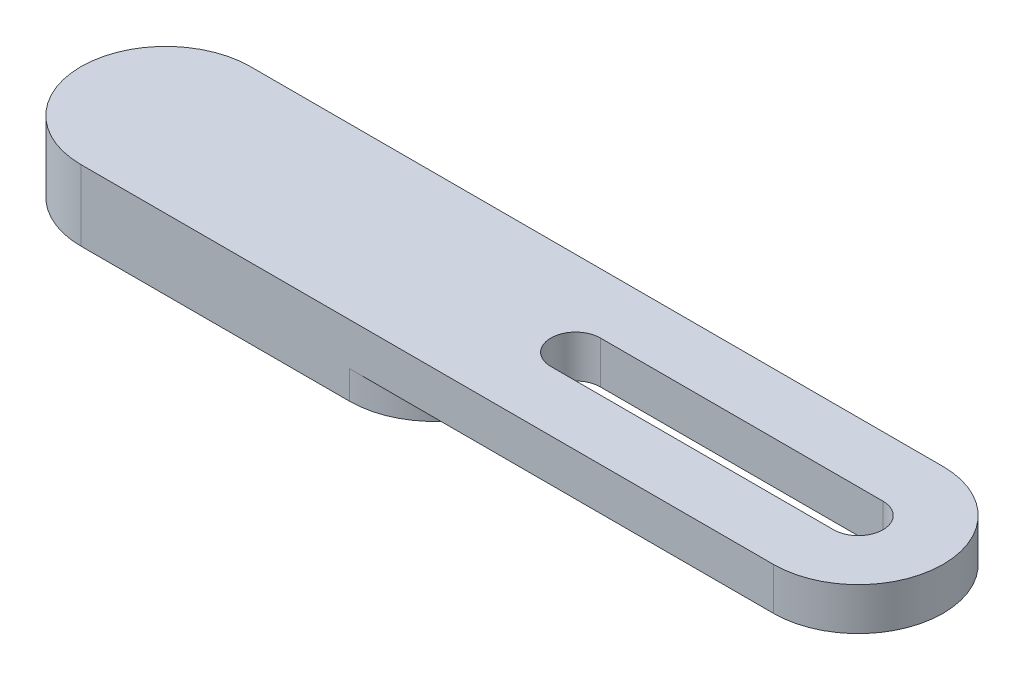
SolidWorks part; units mm, degrees
ref_plane "前视基准面" through (0, 0, 0) normal (0, 0, 1) x (1, 0, 0)
ref_plane "上视基准面" through (0, 0, 0) normal (0, 1, 0) x (1, 0, 0)
ref_plane "右视基准面" through (0, 0, 0) normal (1, 0, 0) x (0, 0, -1)
sketch "草图1" plane through (0, 0, 0) normal (0, 1, 0) x (1, 0, 0)
  line L0 (0, 0) -> (19, 0) construction
  line L1 (0.3158, 3.9875) -> (19.1974, 2.4922)
  line L2 (19.1974, -2.4922) -> (0.3158, -3.9875)
  line L3 (0, 0) -> (-4, 0) construction
  line L4 (19, 0) -> (21.5, 0) construction
  line L5 (19, 6) -> (0, 6)
  line L6 (0, -6) -> (19, -6)
  circle A0 centre (0, 0) radius 4
  circle A1 centre (19, 0) radius 2.5
  circle A2 centre (0, 0) radius 6
  circle A3 centre (19, 0) radius 6
  dimension "D1" = 8
  dimension "D2" = 5
  dimension "D3" = 25.5
  dimension "D4" = 12
  dimension "D5" = 12
extrude "凸台-拉伸1" add sketch "草图1" against normal blind 3 contours L5 | A2 L2 A0 L1 | A3 L5 A2 L1 | A3 L1 A1 L2 | A3 L2 A2 L6 region at (-4.1613, 0, 0) region at (9.6456, 0, -4.7768) region at (16.0449, 0, -5.032) region at (9.6456, 0, 4.7768)
extrude "凸台-拉伸2" add sketch "草图1<4>" along normal blind 2 contours A0 | L2 A2 L1 A0 | A3 L1 A2 L2 | L1 A3 L2 A1 | A1 | A3 L1 A1 L2 | A3 L5 A2 L1 | A3 L2 A2 L6 | A2 L2 A0 L1 region at (-4.1613, 0, 0) region at (4.3016, 0, 0) region at (0, 0, 0) region at (9.6456, 0, -4.7768) region at (9.3099, 0, 0) region at (16.0449, 0, -5.032) region at (15.1794, 0, 0) region at (9.6456, 0, 4.7768) region at (19, 0, 0)
sketch "草图1<4>" plane through (0, 0, 0) normal (0, 1, 0) x (1, 0, 0) same geometry as "草图1"
sketch "草图2" plane through (0, 2, 0) normal (0, 1, 0) x (1, 0, 0)
  line L0 (0, 0) -> (107.5918, 0) construction
  line L1 (49, 1.75) -> (29, 1.75)
  line L2 (0, -6) -> (19, -6)
  line L3 (19, 6) -> (0, 6)
  line L4 (0, -6) -> (19, -6)
  line L5 (19, 6) -> (0, 6)
  line L6 (49, -1.75) -> (29, -1.75)
  line L7 (49, 6) -> (19, 6)
  line L8 (49, -6) -> (19, -6)
  circle A0 centre (29, 0) radius 1.75
  circle A1 centre (49, 0) radius 1.75
  arc A2 (19, -6) -> (19, 6) centre (19, 0) ccw
  arc A3 (0, 6) -> (0, -6) centre (0, 0) ccw
  arc A4 (19, -6) -> (19, 6) centre (19, 0) ccw
  arc A5 (0, 6) -> (0, -6) centre (0, 0) ccw
  circle A6 centre (49, 0) radius 6
  point P17 (52.0747, -6)
  arc M6 (19, -6) -> (19, 6) centre (19, 0) ccw
  dimension "D2" = 3.5
  dimension "D3" = 3.5
  dimension "D5" = 12
  dimension "D6" = 30
  dimension "D4" = 20
  dimension "D1" = 0
extrude "凸台-拉伸3" add sketch "草图2" against normal blind 3 contours L0 L8 A6 L6 A0 M6 | A4 L0 A0 L1 A6 L7 | A1 L0 A6 L1 | L0 A1 L6 A6 region at (49.6581, 2, -3.0421) region at (49.6581, 2, 3.0421) region at (33.6208, 2, -3.8651) region at (33.6208, 2, 3.8651)
